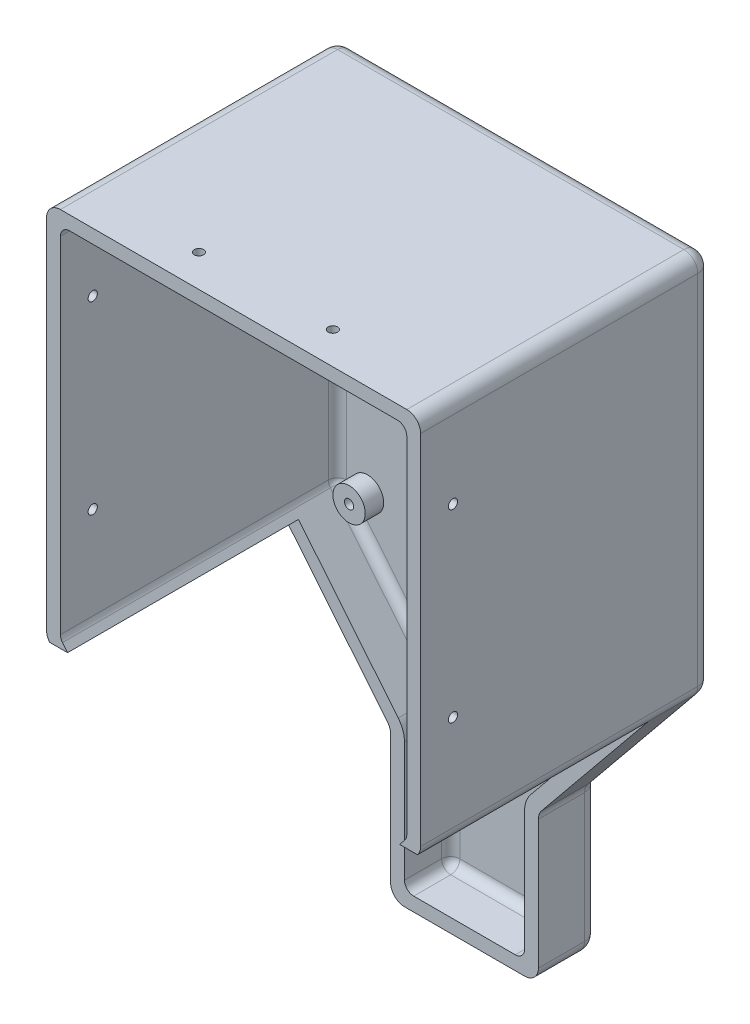
SolidWorks part; units mm, degrees
ref_plane "Front Plane" through (0, 0, 0) normal (0, 0, 1) x (1, 0, 0)
ref_plane "Top Plane" through (0, 0, 0) normal (0, 1, 0) x (1, 0, 0)
ref_plane "Right Plane" through (0, 0, 0) normal (1, 0, 0) x (0, 0, -1)
sketch "Sketch1" plane through (0, 0, 0) normal (0, 0, 1) x (1, 0, 0)
  line L0 (-31, -36) -> (31, 36) construction
  line L1 (-31, -36) -> (31, -36) construction
  line L2 (-31, -36) -> (-31, 36) construction
  line L3 (-31, 36) -> (31, 36) construction
  line L4 (31, -36) -> (31, 36) construction
  circle A0 centre (-31, -36) radius 1
  circle A1 centre (31, -36) radius 1
  circle A2 centre (31, 36) radius 1
  circle A3 centre (-31, 36) radius 1
  circle A4 centre (-31, 36) radius 3.5
  circle A5 centre (31, 36) radius 3.5
  circle A6 centre (31, -36) radius 3.5
  circle A7 centre (-31, -36) radius 3.5
  point P18 (0, 0)
  dimension "D3" = 2
  dimension "D1" = 62
  dimension "D2" = 72
  dimension "D4" = 2.5
extrude "PCB standoffs" add sketch "Sketch1" along normal blind 4
sketch "Sketch2" plane through (0, 0, 0) normal (0, 0, -1) x (-1, 0, 0)
  line L0 (-40.5, -36.4306) -> (-40.5, 41)
  line L1 (-37.5, 44) -> (37.5, 44)
  line L2 (40.5, 41) -> (40.5, -36.4306)
  line L3 (39.8236, -38.3282) -> (16.6764, -66.6718)
  line L4 (16, -68.5694) -> (16, -96.5)
  line L5 (13, -99.5) -> (-13, -99.5)
  line L6 (-16, -96.5) -> (-16, -68.5694)
  line L7 (-16.6764, -66.6718) -> (-39.8236, -38.3282)
  circle A0 centre (31, -36) radius 1 construction
  arc A1 (-13, -99.5) -> (-16, -96.5) centre (-13, -96.5) cw
  arc A2 (16, -96.5) -> (13, -99.5) centre (13, -96.5) cw
  arc A3 (-40.5, -36.4306) -> (-39.8236, -38.3282) centre (-37.5, -36.4306) ccw
  arc A4 (-16, -68.5694) -> (-16.6764, -66.6718) centre (-19, -68.5694) ccw
  arc A5 (16.6764, -66.6718) -> (16, -68.5694) centre (19, -68.5694) ccw
  arc A6 (40.5, -36.4306) -> (39.8236, -38.3282) centre (37.5, -36.4306) cw
  arc A7 (37.5, 44) -> (40.5, 41) centre (37.5, 41) cw
  arc A8 (-40.5, 41) -> (-37.5, 44) centre (-37.5, 41) cw
  point P2 (0, 44)
  point P9 (0, -99.5)
  point P13 (0, 0)
  point P14 (0, 0)
  point P17 (-16, -99.5)
  point P20 (16, -99.5)
  point P23 (-40.5, -37.5)
  point P26 (-16, -67.5)
  point P29 (16, -67.5)
  point P32 (40.5, -37.5)
  point P35 (40.5, 44)
  point P38 (-40.5, 44)
  dimension "D7" = 3
  dimension "D1" = 81
  dimension "D2" = 80
  dimension "D3" = 1.5
  dimension "D4" = 32
  dimension "D5" = 30
  dimension "D6" = 32
extrude "Case backing" add sketch "Sketch2" along normal blind 3
sketch "Sketch3" plane through (0, 0, 0) normal (0, 0, 1) x (1, 0, 0)
  line L0 (13, -96.5) -> (13, -68.5694)
  line L1 (14.3528, -64.7741) -> (37.5, -36.4306)
  line L2 (37.5, -36.4306) -> (37.5, 41)
  line L3 (37.5, 41) -> (-37.5, 41)
  line L4 (-37.5, 41) -> (-37.5, -36.4306)
  line L5 (-37.5, -36.4306) -> (-14.3528, -64.7741)
  line L6 (-13, -68.5694) -> (-13, -96.5)
  line L7 (-13, -96.5) -> (13, -96.5)
  line L8 (16, -96.5) -> (16, -68.5694)
  line L9 (16.6764, -66.6718) -> (39.8236, -38.3282)
  line L10 (40.5, -36.4306) -> (40.5, 41)
  line L11 (37.5, 44) -> (-37.5, 44)
  line L12 (-40.5, 41) -> (-40.5, -36.4306)
  line L13 (-39.8236, -38.3282) -> (-16.6764, -66.6718)
  line L14 (-16, -68.5694) -> (-16, -96.5)
  line L15 (-13, -99.5) -> (13, -99.5)
  line L16 (16, -96.5) -> (16, -68.5694)
  line L17 (16.6764, -66.6718) -> (39.8236, -38.3282)
  line L18 (40.5, -36.4306) -> (40.5, 41)
  line L19 (37.5, 44) -> (-37.5, 44)
  line L20 (-40.5, 41) -> (-40.5, -36.4306)
  line L21 (-39.8236, -38.3282) -> (-16.6764, -66.6718)
  line L22 (-16, -68.5694) -> (-16, -96.5)
  line L23 (-13, -99.5) -> (13, -99.5)
  arc A0 (13, -96.5) -> (13, -96.5) centre (13, -96.5) ccw
  arc A1 (14.3528, -64.7741) -> (13, -68.5694) centre (19, -68.5694) ccw
  arc A2 (37.5, -36.4306) -> (37.5, -36.4306) centre (37.5, -36.4306) ccw
  arc A3 (37.5, 41) -> (37.5, 41) centre (37.5, 41) ccw
  arc A4 (-37.5, 41) -> (-37.5, 41) centre (-37.5, 41) ccw
  arc A5 (-37.5, -36.4306) -> (-37.5, -36.4306) centre (-37.5, -36.4306) ccw
  arc A6 (-13, -68.5694) -> (-14.3528, -64.7741) centre (-19, -68.5694) ccw
  arc A7 (-13, -96.5) -> (-13, -96.5) centre (-13, -96.5) ccw
  arc A8 (13, -99.5) -> (16, -96.5) centre (13, -96.5) ccw
  arc A9 (16.6764, -66.6718) -> (16, -68.5694) centre (19, -68.5694) ccw
  arc A10 (39.8236, -38.3282) -> (40.5, -36.4306) centre (37.5, -36.4306) ccw
  arc A11 (40.5, 41) -> (37.5, 44) centre (37.5, 41) ccw
  arc A12 (-37.5, 44) -> (-40.5, 41) centre (-37.5, 41) ccw
  arc A13 (-40.5, -36.4306) -> (-39.8236, -38.3282) centre (-37.5, -36.4306) ccw
  arc A14 (-16, -68.5694) -> (-16.6764, -66.6718) centre (-19, -68.5694) ccw
  arc A15 (-16, -96.5) -> (-13, -99.5) centre (-13, -96.5) ccw
  arc A16 (13, -99.5) -> (16, -96.5) centre (13, -96.5) ccw
  arc A17 (16.6764, -66.6718) -> (16, -68.5694) centre (19, -68.5694) ccw
  arc A18 (39.8236, -38.3282) -> (40.5, -36.4306) centre (37.5, -36.4306) ccw
  arc A19 (40.5, 41) -> (37.5, 44) centre (37.5, 41) ccw
  arc A20 (-37.5, 44) -> (-40.5, 41) centre (-37.5, 41) ccw
  arc A21 (-40.5, -36.4306) -> (-39.8236, -38.3282) centre (-37.5, -36.4306) ccw
  arc A22 (-16, -68.5694) -> (-16.6764, -66.6718) centre (-19, -68.5694) ccw
  arc A23 (-16, -96.5) -> (-13, -99.5) centre (-13, -96.5) ccw
  dimension "D1" = 0
  dimension "D2" = 3
extrude "Casing sides" add sketch "Sketch3" along normal blind 60
fillet "Casing inner edge fillets 2mm" radius 2 16 edges at (-13, -82.5347, 0) (-13.3483, -66.5548, 0) (13, -82.5347, 0) (13.3483, -66.5548, 0) (37.5, 41, 30) (-37.5, 41, 30) (-37.5, -36.4306, 30) (37.5, -36.4306, 30) (13, -96.5, 30) (-13, -96.5, 30) (0, -96.5, 0) (-25.9264, -50.6024, 0) (25.9264, -50.6024, 0) (37.5, 2.2847, 0) (0, 41, 0) (-37.5, 2.2847, 0)
fillet "Casing outer edge fillets 3mm" radius 3 16 edges at (15.1213, -98.6213, -3) (16, -82.5347, -3) (16.1742, -67.5621, -3) (28.25, -52.5, -3) (40.3258, -37.4379, -3) (40.5, 2.2847, -3) (39.6213, 43.1213, -3) (0, 44, -3) (-39.6213, 43.1213, -3) (-40.5, 2.2847, -3) (-40.3258, -37.4379, -3) (-28.25, -52.5, -3) (-16.1742, -67.5621, -3) (-16, -82.5347, -3) (-15.1213, -98.6213, -3) (0, -99.5, -3)
sketch "Sketch4" plane through (-40.5, 0, 0) normal (-1, 0, 0) x (0, 0, 1)
  line L1 (60, -99.5) -> (10, -99.5)
  line L2 (60, -99.5) -> (60, -38.3282)
  line L3 (60, -38.3282) -> (10, -38.3282)
  line L4 (10, -99.5) -> (10, -38.3282)
  line L5 (0, -38.3282) -> (60, -38.3282) construction
  point P5 (10, -51.7461)
  point P6 (10, -38.3282)
  point P7 (0, 0)
  dimension "D1" = 50
extrude "Bottom casing cut" cut sketch "Sketch4" against normal through all both and the other way through all
sketch "Sketch5" plane through (40.5, 0, 0) normal (1, 0, 0) x (0, 0, -1)
  circle A0 centre (-53, 24.2823) radius 1
  circle A1 centre (-53, -15.7177) radius 1
  circle A2 centre (-53, -15.7177) radius 1 construction
  circle A3 centre (-53, 24.2823) radius 1 construction
extrude "Side screwholes" cut sketch "Sketch5" against normal through all both and the other way through all
sketch "Sketch6" plane through (0, 44, 0) normal (0, 1, 0) x (1, 0, 0)
  circle A4 centre (14.5, -53) radius 1
  circle A5 centre (-14.5, -53) radius 1
  circle A6 centre (14.5, -53) radius 1 construction
  circle A7 centre (-14.5, -53) radius 1 construction
extrude "Top screwholes" cut sketch "Sketch6" against normal through all both and the other way through all
